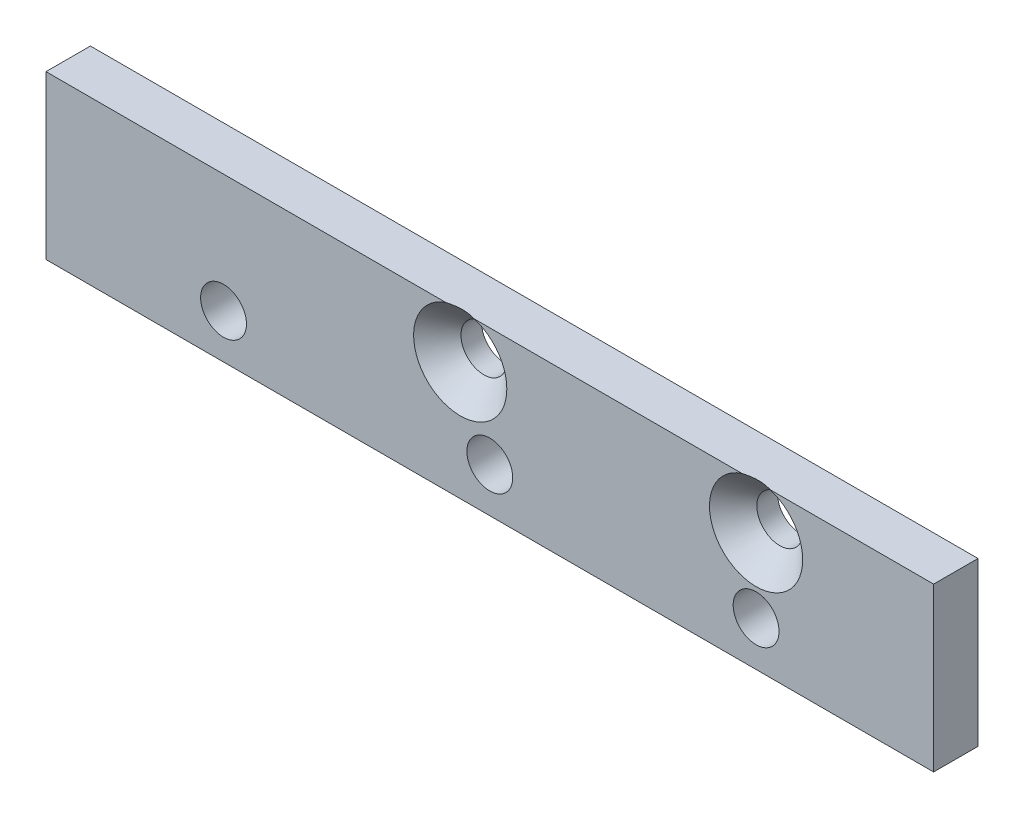
SolidWorks part; units mm, degrees
ref_plane "前视基准面" through (0, 0, 0) normal (0, 0, 1) x (1, 0, 0)
ref_plane "上视基准面" through (0, 0, 0) normal (0, 1, 0) x (1, 0, 0)
ref_plane "右视基准面" through (0, 0, 0) normal (1, 0, 0) x (0, 0, -1)
sketch "草图1" plane through (0, 0, 0) normal (0, 0, 1) x (1, 0, 0)
  line L1 (-30, 5.5) -> (30, 5.5)
  line L2 (-30, 5.5) -> (-30, -5.5)
  line L3 (-30, -5.5) -> (30, -5.5)
  line L4 (30, 5.5) -> (30, -5.5)
  line L5 (-30, 5.5) -> (30, -5.5) construction
  line L6 (-30, -5.5) -> (30, 5.5) construction
  circle A0 centre (18, 2.5) radius 1.55
  circle A1 centre (-2, 2.5) radius 1.55
  circle A2 centre (0, -2.5) radius 1.55
  circle A3 centre (18, -2.5) radius 1.55
  circle A4 centre (-18, -2.5) radius 1.55
  point P0 (0, 0)
  dimension "D3" = 3.1
  dimension "D4" = 3.1
  dimension "D6" = 20
  dimension "D9" = 3.1
  dimension "D10" = 3.1
  dimension "D11" = 3.1
  dimension "D12" = 3
  dimension "D13" = 3
  dimension "D14" = 3
  dimension "D1" = 11
  dimension "D2" = 60
  dimension "D5" = 12
  dimension "D7" = 3
  dimension "D8" = 3
  dimension "D15" = 30
  dimension "D16" = 12
  dimension "D17" = 18
extrude "凸台-拉伸1" add sketch "草图1" along normal blind 3
chamfer "倒角1" distance 1.6 angle 45 2 edges at (19.55, 2.5, 3) (-0.45, 2.5, 3)
